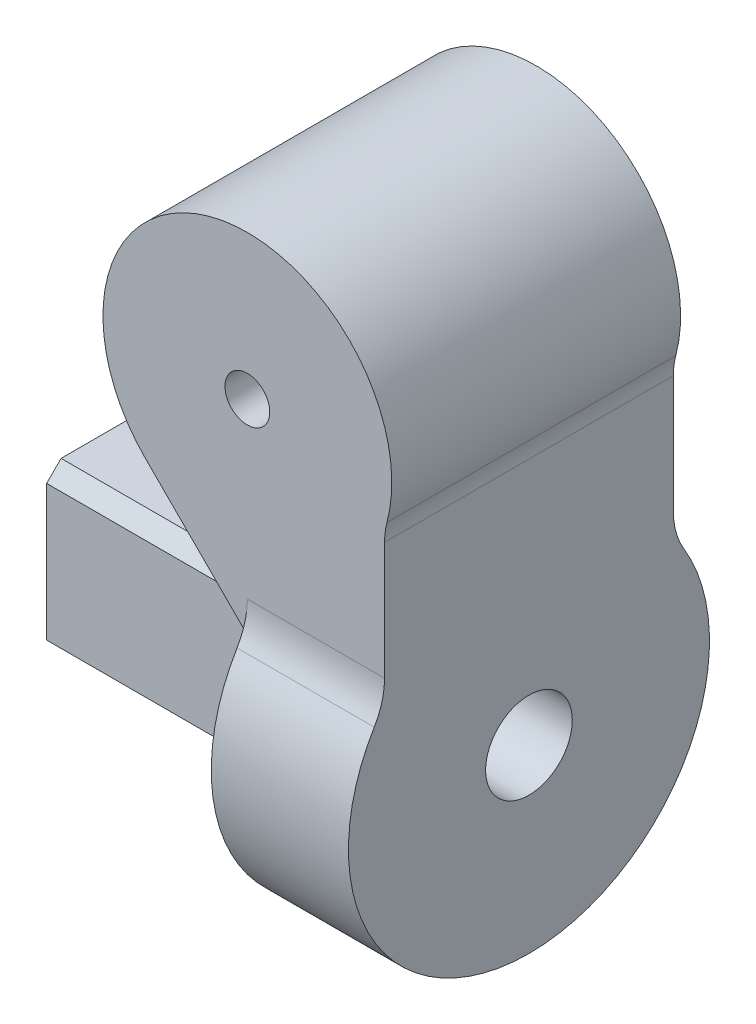
SolidWorks part; units mm, degrees
ref_plane "Front Plane" through (0, 0, 0) normal (0, 0, 1) x (1, 0, 0)
ref_plane "Top Plane" through (0, 0, 0) normal (0, 1, 0) x (1, 0, 0)
ref_plane "Right Plane" through (0, 0, 0) normal (1, 0, 0) x (0, 0, -1)
sketch "Sketch1" plane through (0, 0, 0) normal (1, 0, 0) x (0, 0, -1)
  circle A0 centre (0, 0) radius 62.5
  circle A1 centre (0, 0) radius 15
  dimension "D1" = 125
  dimension "D2" = 30
extrude "Boss-Extrude1" add sketch "Sketch1" along normal blind 47.5
sketch "Sketch2" plane through (0, 0, 0) normal (0, 0, 1) x (1, 0, 0)
  line L1 (0, 0) -> (0, 105) construction
  line L2 (-35.3553, 69.6447) -> (0, 34.2893)
  line L3 (0, 34.2893) -> (0, 55)
  arc A0 (0, 55) -> (-35.3553, 69.6447) centre (0, 105) ccw
  circle A1 centre (0, 105) radius 32.5
  arc A2 (-35.3553, 69.6447) -> (0, 55) centre (0, 105) ccw construction
  dimension "D1" = 100
  dimension "D2" = 65
  dimension "D3" = 105
  dimension "D4" = 45
extrude "Boss-Extrude2" add sketch "Sketch2" along normal mid plane 100
sketch "Sketch3" plane through (47.5, 0, 0) normal (1, 0, 0) x (0, 0, -1)
  line L0 (-50, 55) -> (-50, 62.5)
  line L1 (-50, 155) -> (-50, 55) construction
  line L2 (-50, 55) -> (-50, 37.5)
  line L3 (-29.6859, 55) -> (-50, 55)
  line L4 (-50, 55) -> (-50, 37.5)
  line L6 (50, 55) -> (29.6859, 55)
  line L7 (50, 37.5) -> (50, 55)
  line L9 (50, 37.5) -> (50, 55)
  line L10 (-50, 62.5) -> (50, 62.5)
  line L11 (50, 55) -> (50, 155) construction
  line L12 (50, 62.5) -> (50, 55)
  line L13 (29.6859, 55) -> (-29.6859, 55)
  circle A0 centre (0, 0) radius 62.5 construction
  arc A1 (-29.6859, 55) -> (-50, 37.5) centre (0, 0) ccw
  arc A2 (-29.6859, 55) -> (-50, 37.5) centre (0, 0) ccw
  arc A3 (50, 37.5) -> (29.6859, 55) centre (0, 0) ccw
  arc A4 (50, 37.5) -> (29.6859, 55) centre (0, 0) ccw
  dimension "D1" = 0
  dimension "D2" = 0
extrude "Boss-Extrude3" add sketch "Sketch3" against normal up to surface (47.5 mm away) up to face at (0, 49.5341, 43.5451)
sketch "Sketch4" plane through (0, 0, 50) normal (0, 0, 1) x (1, 0, 0)
  line L0 (47.5, 62.5) -> (47.5, 89.3875)
  line L1 (26.3391, 62.5) -> (47.5, 62.5) construction
  line L2 (26.3391, 62.5) -> (47.5, 62.5)
  arc A0 (26.3391, 62.5) -> (-35.3553, 69.6447) centre (0, 105) ccw construction
  arc A1 (26.3391, 62.5) -> (-35.3553, 69.6447) centre (0, 105) ccw
  line M2 (47.5, 62.5) -> (26.3391, 62.5)
  arc M3 (26.3391, 62.5) -> (-35.3553, 69.6447) centre (0, 105) ccw
extrude "Boss-Extrude4" add sketch "Sketch4" against normal up to surface (100 mm away) contours L0 M2 M3 region at (41.2754, 70.2611, 50) up to face at (16.0406, 65.4216, -50)
fillet "Fillet1" radius 25 3 edges at (23.75, 37.5, -50) (23.75, 37.5, 50) (47.5, 89.3875, 0)
sketch "Sketch5" plane through (0, 0, 0) normal (-1, 0, 0) x (0, 0, 1)
  line L1 (-28.5, -28.5) -> (28.5, -28.5)
  line L2 (-28.5, -28.5) -> (-28.5, 28.5)
  line L3 (-28.5, 28.5) -> (28.5, 28.5)
  line L4 (28.5, -28.5) -> (28.5, 28.5)
  line L5 (-28.5, -28.5) -> (28.5, 28.5) construction
  line L6 (-28.5, 28.5) -> (28.5, -28.5) construction
  point P0 (0, 0)
  dimension "D1" = 57
extrude "Boss-Extrude5" add sketch "Sketch5" along normal blind 91
chamfer "Chamfer1" distance 5 angle 45 4 edges at (-45.5, -28.5, 28.5) (-45.5, -28.5, -28.5) (-45.5, 28.5, 28.5) (-45.5, 28.5, -28.5)
sketch "Sketch6" plane through (0, 0, 50) normal (0, 0, 1) x (1, 0, 0)
  circle A0 centre (0, 105) radius 37.75
  dimension "D1" = 75.5
extrude "Cut-Extrude1" cut sketch "Sketch6" against normal up to surface (100 mm away) up to face at (14.7119, 74.0752, -50)
ref_plane "Plane1" through (0, 0, 0) normal (0, 0, 1) x (1, 0, 0)
sketch "Sketch8" plane through (0, 0, 0) normal (0, 0, 1) x (1, 0, 0)
  circle A0 centre (0, 105) radius 45
  dimension "D1" = 90
extrude "Cut-Extrude2" cut sketch "Sketch8" against normal blind 5 and the other way blind 5
ref_plane "Plane2" through (0, 0, -40) normal (0, 0, -1) x (-1, 0, 0)
sketch "Sketch9" plane through (0, 0, -40) normal (0, 0, -1) x (-1, 0, 0)
  circle A0 centre (0, 105) radius 45
  dimension "D1" = 90
extrude "Cut-Extrude3" cut sketch "Sketch9" against normal blind 5 and the other way blind 5
sketch "Sketch12" plane through (0, 0, 50) normal (0, 0, 1) x (1, 0, 0)
  circle A0 centre (0, 105) radius 37.75
extrude "Boss-Extrude6" add sketch "Sketch12" against normal blind 30
sketch "Sketch13" plane through (0, 0, 20) normal (0, 0, -1) x (-1, 0, 0)
  circle A0 centre (0, 105) radius 7.75
  dimension "D1" = 15.5
extrude "Cut-Extrude5" cut sketch "Sketch13" against normal up to surface (30 mm away) up to face at (14.7119, 74.0752, 50)
sketch "Sketch15" plane through (0, 0, 20) normal (0, 0, -1) x (-1, 0, 0)
  line L0 (0, 105) -> (0, 131.433) construction
  circle A0 centre (0, 117.5) radius 1.4
  dimension "D1" = 2.8
  dimension "D2" = 12.5
extrude "Cut-Extrude7" cut sketch "Sketch15" against normal blind 5
pattern_circular "CirPattern2" count 3 every 120 about axis through (0, 105, 20) along (0, 0, -1) of "Cut-Extrude7"
